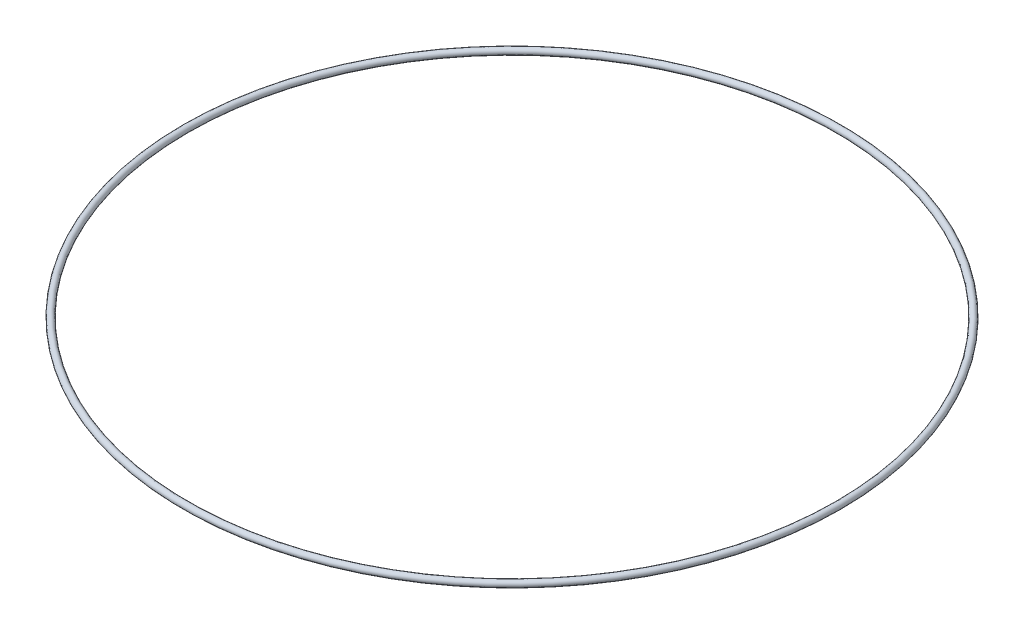
SolidWorks part; units mm, degrees
ref_plane "Front Plane" through (0, 0, 0) normal (0, 0, 1) x (1, 0, 0)
ref_plane "Top Plane" through (0, 0, 0) normal (0, 1, 0) x (1, 0, 0)
ref_plane "Right Plane" through (0, 0, 0) normal (1, 0, 0) x (0, 0, -1)
sketch "Sketch1" plane through (0, 0, 0) normal (0, 1, 0) x (1, 0, 0)
  circle A0 centre (0, 0) radius 127
sketch "Sketch2" plane through (0, 0, 0) normal (0, 0, 1) x (1, 0, 0)
  line L0 (127, 0) -> (-127, 0) construction
  circle A0 centre (-127, 0) radius 1.27
  point P4 (-127, 0)
sweep "Sweep1" add profiles "Sketch2" path "Sketch1"
